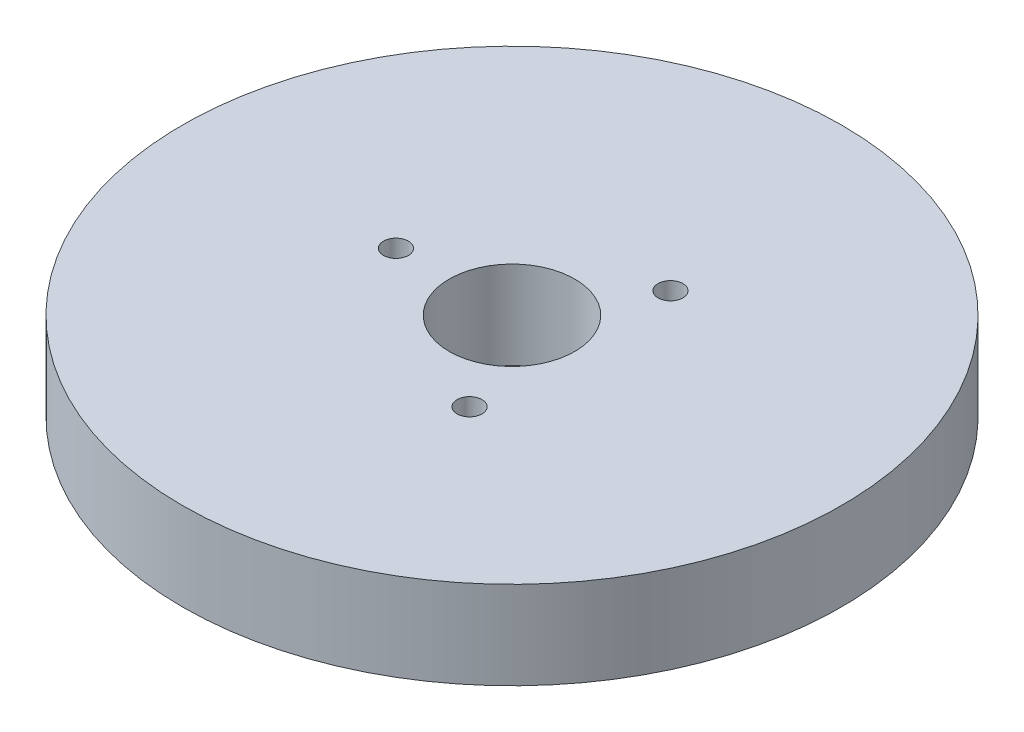
SolidWorks part; units mm, degrees
ref_plane "Front Plane" through (0, 0, 0) normal (0, 0, 1) x (1, 0, 0)
ref_plane "Top Plane" through (0, 0, 0) normal (0, 1, 0) x (1, 0, 0)
ref_plane "Right Plane" through (0, 0, 0) normal (1, 0, 0) x (0, 0, -1)
sketch "Sketch1" plane through (0, 0, 0) normal (0, 1, 0) x (1, 0, 0)
  circle A0 centre (0, 0) radius 52.5
  dimension "FLANGE_OD" = 105
extrude "Boss-Extrude1" add sketch "Sketch1" along normal blind 14
sketch "Sketch2" plane through (0, 0, 0) normal (0, 1, 0) x (1, 0, 0)
  circle A0 centre (0, 0) radius 10
  dimension "BORE_D" = 20
extrude "Cut-Extrude1" cut sketch "Sketch2" along normal through all
sketch "Sketch3" plane through (0, 14, 0) normal (0, 1, 0) x (1, 0, 0)
  circle A0 centre (0, 0) radius 18.4831 construction
  circle A1 centre (-18.4831, 0) radius 1.9821
  dimension "BOLT_D" = 3.9642
  dimension "BOLT_PCD" = 36.9662
extrude "Cut-Extrude2" cut sketch "Sketch3" against normal blind 13.5697
pattern_circular "CirPattern1" count 3 over 360 about axis through (0, 0, 0) along (0, 1, 0) of "Cut-Extrude2"
